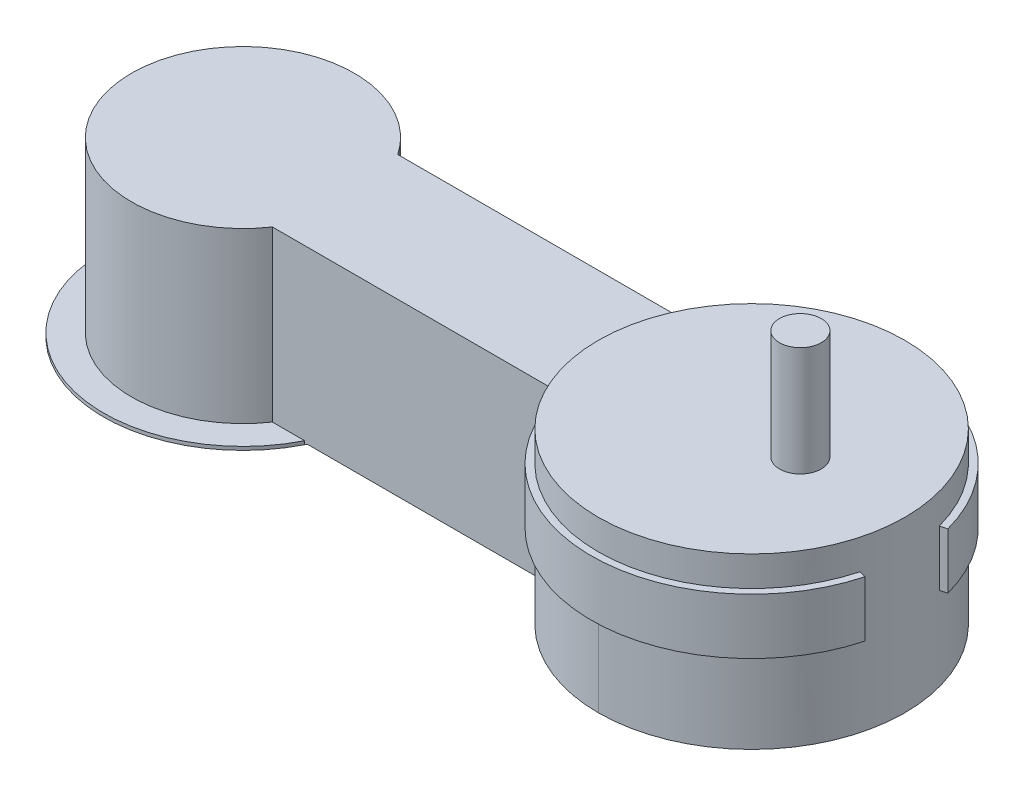
SolidWorks part; units mm, degrees
ref_plane "Front Plane" through (0, 0, 0) normal (0, 0, 1) x (1, 0, 0)
ref_plane "Top Plane" through (0, 0, 0) normal (0, 1, 0) x (1, 0, 0)
ref_plane "Right Plane" through (0, 0, 0) normal (1, 0, 0) x (0, 0, -1)
sketch "Sketch1" plane through (0, 0, 0) normal (0, 1, 0) x (1, 0, 0)
  line L0 (101.7992, 28.575) -> (-84.9987, 28.575)
  line L3 (-84.9987, -28.575) -> (101.7992, -28.575)
  arc A0 (101.7992, -28.575) -> (101.7992, 28.575) centre (127, 0) ccw
  arc A1 (-84.9987, -28.575) -> (-84.9987, 28.575) centre (-127, 0) cw
  point P0 (0, 0)
  dimension "D4" = 38.1
  dimension "D6" = 50.8
  dimension "D1" = 57.15
  dimension "D2" = 28.575
  dimension "D3" = 127
  dimension "D5" = 127
extrude "Boss-Extrude1" add sketch "Sketch1" along normal blind 1.5875
sketch "Sketch2" plane through (0, 1.5875, 0) normal (0, 1, 0) x (1, 0, 0)
  circle A0 centre (-127, 0) radius 9.525
  circle A1 centre (127, 0) radius 9.525
  dimension "D1" = 19.05
  dimension "D2" = 19.05
extrude "Boss-Extrude2" add sketch "Sketch2" along normal blind 76.2 and the other way blind 39.624 contours A0
sketch "Sketch4" plane through (0, 1.5875, 0) normal (0, 1, 0) x (1, 0, 0)
  circle A0 centre (127, 0) radius 9.525
  dimension "D1" = 19.05
extrude "Boss-Extrude3" add sketch "Sketch4" along normal blind 127 and the other way blind 28.575
ref_plane "Plane1" through (0, 76.2, 0) normal (0, 1, 0) x (1, 0, 0)
sketch "Sketch5" plane through (0, 76.2, 0) normal (0, 1, 0) x (1, 0, 0)
  line L0 (-55, 0) -> (55, 0) construction
  circle A0 centre (127, 0) radius 9.525 construction
  circle A1 centre (127, 0) radius 9.525 construction
  circle A4 centre (104.775, 0) radius 69.85
  circle A5 centre (104.775, 0) radius 63.5
  dimension "D1" = 139.7
  dimension "D2" = 22.225
  dimension "D3" = 127
extrude "Boss-Extrude4" add sketch "Sketch5" against normal up to surface (74.6125 mm away) up to face at (127, 1.5875, -9.525)
sketch "Sketch6" plane through (0, 76.2, 0) normal (0, 1, 0) x (1, 0, 0)
  circle A0 centre (104.775, 0) radius 69.85 construction
  circle A4 centre (104.775, 0) radius 69.85
  point P0 (104.775, 0)
extrude "Boss-Extrude5" add sketch "Sketch6" along normal blind 2.54
sketch "Sketch10" plane through (0, 0, 0) normal (0, -1, 0) x (1, 0, 0)
  line L2 (-84.9987, -28.575) -> (101.7992, -28.575)
  line L3 (101.7992, 28.575) -> (-84.9987, 28.575)
  line L4 (48.0677, -28.575) -> (101.7992, -28.575)
  line L5 (101.7992, 28.575) -> (48.0677, 28.575)
  arc A2 (-84.9987, 28.575) -> (-84.9987, -28.575) centre (-127, 0) ccw
  arc A3 (101.7992, -28.575) -> (101.7992, 28.575) centre (127, 0) ccw
  arc A5 (101.7992, -28.575) -> (101.7992, 28.575) centre (127, 0) ccw
  circle A6 centre (127, 0) radius 9.525 construction
  circle A7 centre (127, 0) radius 9.525
  arc A8 (48.0677, 28.575) -> (48.0677, -28.575) centre (104.775, 0) ccw construction
  arc A9 (48.0677, 28.575) -> (48.0677, -28.575) centre (104.775, 0) ccw
  dimension "D1" = 0
extrude "Cut-Extrude3" cut sketch "Sketch10" against normal up to next
ref_plane "Plane2" through (0, 1.5875, 0) normal (0, -1, 0) x (-1, 0, 0)
sketch "Sketch11" plane through (0, 1.5875, 0) normal (0, -1, 0) x (-1, 0, 0)
  circle A0 centre (-127, 0) radius 9.525 construction
  circle A1 centre (-127, 0) radius 9.525
  circle A2 centre (-127, 0) radius 31.75
  dimension "D1" = 63.5
extrude "Boss-Extrude6" add sketch "Sketch11" along normal blind 1.5875
sketch "Sketch13" plane through (0, 1.5875, 0) normal (0, 1, 0) x (1, 0, 0)
  line L0 (-84.9987, -28.575) -> (41.0373, -28.575) construction
  line L1 (41.0373, 28.575) -> (-84.9987, 28.575) construction
  line L2 (-84.9987, -28.575) -> (41.0373, -28.575)
  line L3 (41.0373, 28.575) -> (-84.9987, 28.575)
  line L6 (-86.365, -26.035) -> (37.2288, -26.035)
  line L7 (37.2288, 26.035) -> (-86.365, 26.035)
  arc A1 (-84.9987, 28.575) -> (-84.9987, -28.575) centre (-127, 0) ccw construction
  arc A3 (-84.9987, 28.575) -> (-84.9987, -28.575) centre (-127, 0) ccw
  arc A6 (-86.365, 26.035) -> (-86.365, -26.035) centre (-127, 0) ccw
  arc A7 (41.0373, 28.575) -> (41.0373, -28.575) centre (104.775, 0) ccw construction
  arc A8 (41.0373, 28.575) -> (41.0373, -28.575) centre (104.775, 0) ccw
  arc A9 (37.2288, 26.035) -> (37.2288, -26.035) centre (104.775, 0) ccw
  dimension "D1" = 2.54
extrude "Boss-Extrude7" add sketch "Sketch13" along normal blind 76.2
sketch "Sketch14" plane through (0, 77.7875, 0) normal (0, 1, 0) x (1, 0, 0)
  line L4 (-86.365, -26.035) -> (37.2288, -26.035) construction
  line L5 (37.2288, 26.035) -> (-86.365, 26.035) construction
  line L6 (-86.365, -26.035) -> (37.2288, -26.035)
  line L7 (37.2288, 26.035) -> (-86.365, 26.035)
  arc A5 (37.2288, 26.035) -> (37.2288, -26.035) centre (104.775, 0) ccw construction
  arc A6 (-86.365, 26.035) -> (-86.365, -26.035) centre (-127, 0) ccw construction
  arc A7 (37.2288, 26.035) -> (37.2288, -26.035) centre (104.775, 0) ccw
  arc A8 (-86.365, 26.035) -> (-86.365, -26.035) centre (-127, 0) ccw
extrude "Boss-Extrude8" add sketch "Sketch14" against normal blind 1.5875
ref_plane "Plane3" through (0, 39.6875, 0) normal (0, -1, 0) x (-1, 0, 0)
sketch "Sketch18" plane through (0, 39.6875, 0) normal (0, -1, 0) x (-1, 0, 0)
  line L0 (84.9987, -28.575) -> (-48.0677, -28.575) construction
  line L1 (-41.0373, 28.575) -> (-37.5729, 28.575)
  line L2 (-41.0373, -28.575) -> (-37.5729, -28.575)
  line L3 (-104.775, 0) -> (-194.6436, 24.0802) construction
  line L4 (-104.775, 0) -> (-208.3608, -27.7557) construction
  line L5 (-104.775, 0) -> (-234.0175, 0) construction
  line L6 (-175.3117, 18.9003) -> (-172.2449, 18.0785)
  line L7 (-175.3117, -18.9003) -> (-172.2449, -18.0785)
  arc A3 (-37.5729, 28.575) -> (-175.3117, 18.9003) centre (-104.775, 0) ccw
  arc A4 (-41.0373, 28.575) -> (-172.2449, 18.0785) centre (-104.775, 0) ccw
  arc A5 (-175.3117, -18.9003) -> (-37.5729, -28.575) centre (-104.775, 0) ccw
  arc A6 (-172.2449, -18.0785) -> (-41.0373, -28.575) centre (-104.775, 0) ccw
  dimension "D1" = 73.025
  dimension "D2" = 15
  dimension "D3" = 30
  dimension "D4" = 104.775
extrude "Boss-Extrude9" add sketch "Sketch18" against normal blind 25.4
sketch "Sketch19" plane through (0, 0, 0) normal (0, -1, 0) x (1, 0, 0)
  circle A0 centre (-127, 0) radius 63.5
  dimension "D1" = 127
extrude "Boss-Extrude10" add sketch "Sketch19" along normal mid plane 1.5875
fillet "Fillet1" radius 2.54 1 edges at (-63.5, 0, 0)
